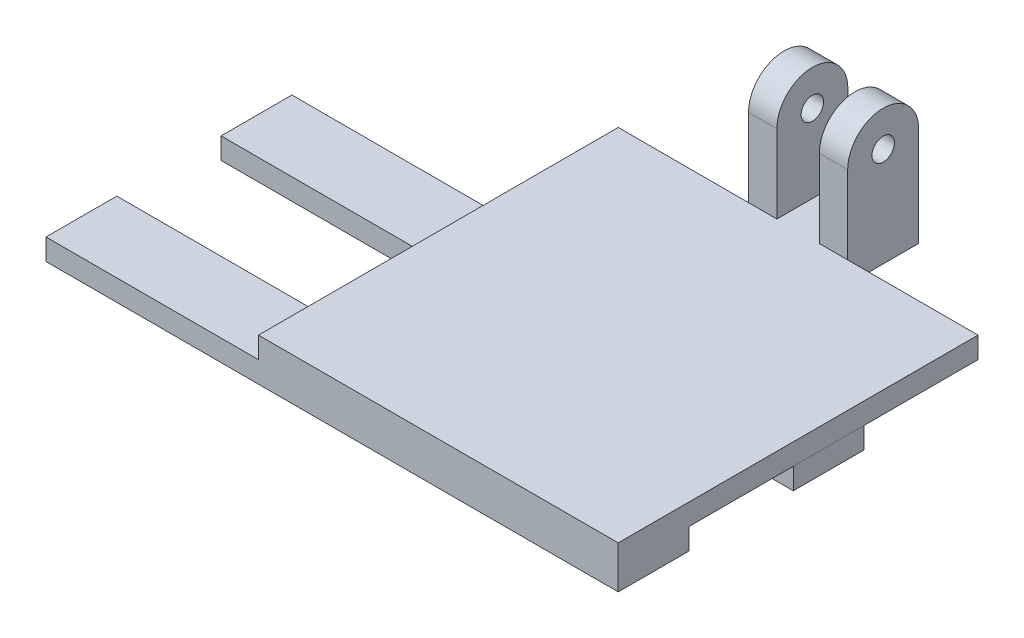
SolidWorks part; units mm, degrees
ref_plane "Front Plane" through (0, 0, 0) normal (0, 0, 1) x (1, 0, 0)
ref_plane "Top Plane" through (0, 0, 0) normal (0, 1, 0) x (1, 0, 0)
ref_plane "Right Plane" through (0, 0, 0) normal (1, 0, 0) x (0, 0, -1)
sketch "Sketch1" plane through (0, 0, 0) normal (0, 1, 0) x (1, 0, 0)
  line L1 (0, 0) -> (50.8, 0)
  line L2 (0, 0) -> (0, 50.8)
  line L3 (0, 50.8) -> (50.8, 50.8)
  line L4 (50.8, 0) -> (50.8, 50.8)
  line L5 (18.4, 50.8) -> (32.4, 50.8)
  line L6 (18.4, 50.8) -> (18.4, 60.8232)
  line L7 (18.4, 60.8232) -> (32.4, 60.8232)
  line L8 (32.4, 50.8) -> (32.4, 60.8232)
  line L9 (18.4, 50.8) -> (22.4, 50.8)
  line L10 (18.4, 50.8) -> (18.4, 60.8232)
  line L11 (18.4, 60.8232) -> (22.4, 60.8232)
  line L12 (22.4, 50.8) -> (22.4, 60.8232)
  line L13 (32.4, 50.8) -> (28.4, 50.8)
  line L14 (32.4, 50.8) -> (32.4, 60.8232)
  line L15 (32.4, 60.8232) -> (28.4, 60.8232)
  line L16 (28.4, 50.8) -> (28.4, 60.8232)
  dimension "D1" = 50.8
  dimension "D2" = 50.8
  dimension "D3" = 14
  dimension "D4" = 18.4
  dimension "D5" = 4
  dimension "D6" = 4
extrude "Boss-Extrude1" add sketch "Sketch1" along normal blind 3 contours L1 L4 L3 L5 L2 | L5 L16 L7 L12 region at (25.4, 0, -25.4) region at (25.4, 0, -55.8116)
extrude "Boss-Extrude2" add sketch "Sketch1<3>" along normal blind 19.05 contours L16 L3 L8 L7 | L3 L12 L7 L6 region at (20.4, 0, -55.8116) region at (30.4, 0, -55.8116)
sketch "Sketch1<3>" plane through (0, 0, 0) normal (0, 1, 0) x (1, 0, 0) same geometry as "Sketch1"
sketch "Sketch2" plane through (32.4, 0, 0) normal (1, 0, 0) x (0, 0, -1)
  line L0 (50.8, 14.0384) -> (49.9115, 20.3951)
  line L1 (60.8232, 19.05) -> (60.8232, 0) construction
  line L2 (49.9115, 20.3951) -> (64.5018, 21.2477)
  line L3 (50.8, 19.05) -> (50.8, 3) construction
  line L4 (64.5018, 21.2477) -> (60.8232, 14.0384)
  arc A0 (50.8, 14.0384) -> (60.8232, 14.0384) centre (55.8116, 14.0384) cw
  circle A1 centre (55.8116, 14.0384) radius 1.5875
  dimension "D1" = 3.175
extrude "Cut-Extrude1" cut sketch "Sketch2" against normal blind 19.05
sketch "Sketch3" plane through (0, 0, 0) normal (0, -1, 0) x (1, 0, 0)
  line L0 (0, 0) -> (-30, 0)
  line L1 (-30, 0) -> (-30, -10)
  line L2 (-30, -10) -> (50.8, -10)
  line L3 (50.8, 0) -> (50.8, -50.8) construction
  line L4 (50.8, -10) -> (50.8, 0)
  line L5 (50.8, 0) -> (0, 0)
  line L7 (50.7964, -24.7232) -> (-30, -24.7232)
  line L8 (50.7964, -24.7232) -> (50.7964, -34.7232)
  line L9 (50.7964, -34.7232) -> (-30, -34.7232)
  line L10 (-30, -24.7232) -> (-30, -34.7232)
  dimension "D1" = 30
  dimension "D2" = 10
  dimension "D3" = 10
extrude "Boss-Extrude3" add sketch "Sketch3" along normal blind 3
